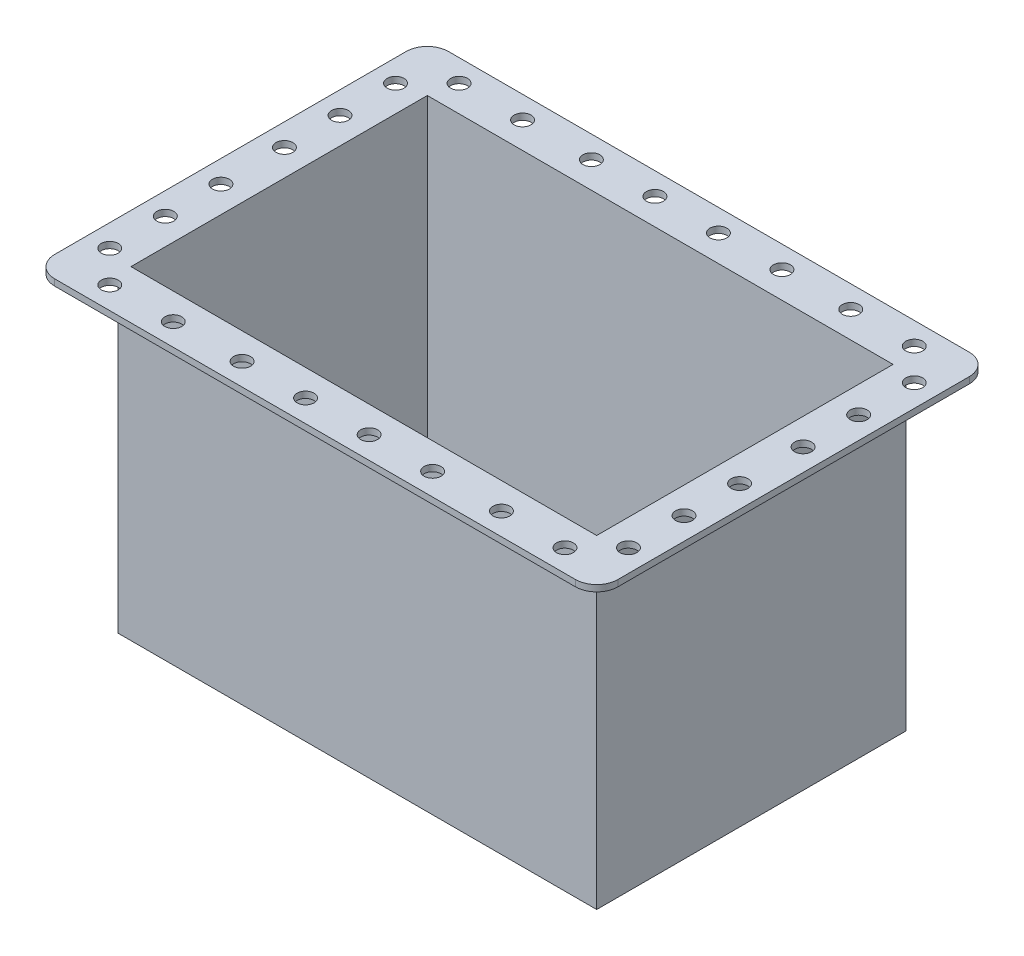
SolidWorks part; units mm, degrees
material "5052-H32"
ref_plane "Front Plane" through (0, 0, 0) normal (0, 0, 1) x (1, 0, 0)
ref_plane "Top Plane" through (0, 0, 0) normal (0, 1, 0) x (1, 0, 0)
ref_plane "Right Plane" through (0, 0, 0) normal (1, 0, 0) x (0, 0, -1)
sketch "Sketch1" plane through (0, 0, 0) normal (0, 1, 0) x (1, 0, 0)
  line L0 (-113, 73) -> (-113, -73)
  line L1 (-110, 70) -> (110, 70)
  line L2 (-110, 70) -> (-110, -70)
  line L3 (-110, -70) -> (110, -70)
  line L4 (110, 70) -> (110, -70)
  line L5 (-110, 70) -> (110, -70) construction
  line L6 (-110, -70) -> (110, 70) construction
  line L7 (-113, -73) -> (113, -73)
  line L8 (113, 73) -> (113, -73)
  line L9 (-113, 73) -> (113, 73)
  point P4 (0, 0)
  dimension "D1" = 220
  dimension "D2" = 140
  dimension "D3" = 3
extrude "Boss-Extrude1" add sketch "Sketch1" along normal blind 150
extrude "Boss-Extrude2" add sketch "Sketch1<4>" along normal blind 3 contours L2 L3 L4 L1
sketch "Sketch1<4>" plane through (0, 0, 0) normal (0, 1, 0) x (1, 0, 0) same geometry as "Sketch1"
sketch "Sketch2" plane through (0, 150, 0) normal (0, 1, 0) x (1, 0, 0)
  line L8 (110, 70) -> (-110, 70)
  line L9 (-110, 70) -> (-110, -70)
  line L10 (-110, -70) -> (110, -70)
  line L11 (110, -70) -> (110, 70)
  line L12 (110, 70) -> (-110, 70)
  line L13 (-110, 70) -> (-110, -70)
  line L14 (-110, -70) -> (110, -70)
  line L15 (110, -70) -> (110, 70)
  line L26 (-133, -93) -> (133, -93)
  line L27 (133, -93) -> (133, 93)
  line L28 (133, 93) -> (-133, 93)
  line L29 (-133, 93) -> (-133, -93)
  line L30 (-133, -93) -> (133, -93)
  line L31 (133, -93) -> (133, 93)
  line L32 (133, 93) -> (-133, 93)
  line L33 (-133, 93) -> (-133, -93)
  dimension "D1" = 3
  dimension "D2" = 20
extrude "Boss-Extrude3" add sketch "Sketch2" against normal blind 3
fillet "Fillet1" radius 10 4 edges at (133, 148.5, -93) (-133, 148.5, -93) (133, 148.5, 93) (-133, 148.5, 93)
sketch "Sketch3" plane through (0, 150, 0) normal (0, 1, 0) x (1, 0, 0)
  line L10 (-122.5, 0) -> (122.5, 0) construction
  line L11 (0, 82.5) -> (0, -82.5) construction
  line L14 (-122.5, -82.5) -> (122.5, -82.5)
  line L15 (122.5, -82.5) -> (122.5, 82.5)
  line L16 (122.5, 82.5) -> (-122.5, 82.5)
  line L17 (-122.5, 82.5) -> (-122.5, -82.5)
  line L18 (-122.5, -82.5) -> (122.5, -82.5) construction
  line L19 (122.5, -82.5) -> (122.5, 82.5) construction
  line L20 (122.5, 82.5) -> (-122.5, 82.5) construction
  line L21 (-122.5, 82.5) -> (-122.5, -82.5) construction
  circle A0 centre (-122.5, -15) radius 4
  circle A1 centre (-122.5, -41.25) radius 4
  circle A2 centre (-122.5, -67.5) radius 4
  circle A3 centre (-107.5, -82.5) radius 4
  circle A4 centre (-77.5, -82.5) radius 4
  circle A5 centre (-45, -82.5) radius 4
  circle A6 centre (-15, -82.5) radius 4
  circle A7 centre (-45, 82.5) radius 4
  circle A8 centre (-15, 82.5) radius 4
  circle A9 centre (-77.5, 82.5) radius 4
  circle A10 centre (-107.5, 82.5) radius 4
  circle A11 centre (-122.5, 67.5) radius 4
  circle A12 centre (-122.5, 41.25) radius 4
  circle A13 centre (-122.5, 15) radius 4
  circle A14 centre (15, -82.5) radius 4
  circle A15 centre (45, -82.5) radius 4
  circle A16 centre (107.5, -82.5) radius 4
  circle A17 centre (122.5, -67.5) radius 4
  circle A18 centre (122.5, -41.25) radius 4
  circle A19 centre (122.5, -15) radius 4
  circle A20 centre (122.5, 15) radius 4
  circle A21 centre (122.5, 41.25) radius 4
  circle A22 centre (122.5, 67.5) radius 4
  circle A23 centre (107.5, 82.5) radius 4
  circle A24 centre (77.5, 82.5) radius 4
  circle A25 centre (45, 82.5) radius 4
  circle A26 centre (15, 82.5) radius 4
  circle A27 centre (77.5, -82.5) radius 4
  dimension "D9" = 8
  dimension "D2" = 15
  dimension "D3" = 41.25
  dimension "D4" = 15
  dimension "D5" = 15
  dimension "D6" = 15
  dimension "D7" = 45
  dimension "D8" = 45
  dimension "D1" = 12.5
extrude "Cut-Extrude1" cut sketch "Sketch3" against normal through all
